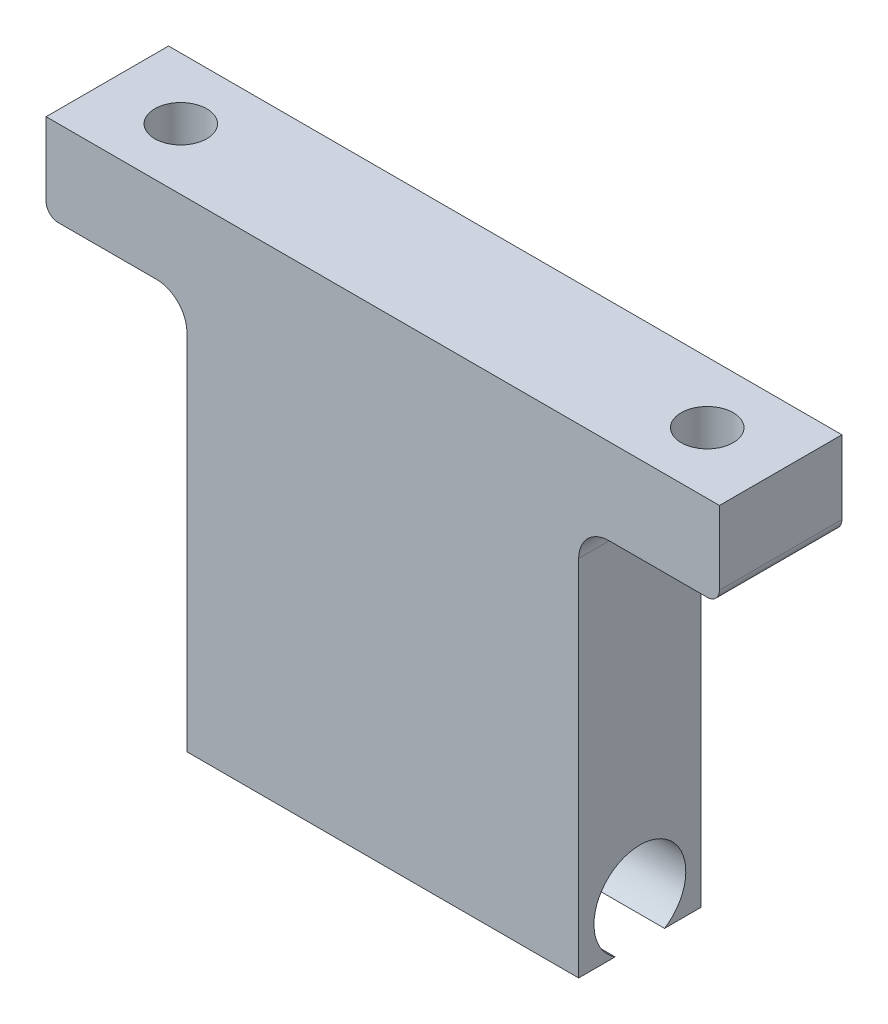
SolidWorks part; units mm, degrees
ref_plane "Front Plane" through (0, 0, 0) normal (0, 0, 1) x (1, 0, 0)
ref_plane "Top Plane" through (0, 0, 0) normal (0, 1, 0) x (1, 0, 0)
ref_plane "Right Plane" through (0, 0, 0) normal (1, 0, 0) x (0, 0, -1)
sketch "Esboço2" plane through (0, 0, 0) normal (0, 0, 1) x (1, 0, 0)
  line L1 (-252, 105.2122) -> (-188, 105.2122)
  line L2 (-252, 105.2122) -> (-252, 164.5682)
  line L4 (-188, 105.2122) -> (-188, 164.5682)
  line L9 (-183, 169.5682) -> (-167, 169.5682)
  line L10 (-165, 171.5682) -> (-165, 183.5682)
  line L11 (-165, 183.5682) -> (-275, 183.5682)
  line L12 (-275, 183.5682) -> (-275, 171.5682)
  line L13 (-273, 169.5682) -> (-257, 169.5682)
  arc A4 (-183, 169.5682) -> (-188, 164.5682) centre (-183, 164.5682) ccw
  arc A5 (-167, 169.5682) -> (-165, 171.5682) centre (-167, 171.5682) ccw
  arc A6 (-275, 171.5682) -> (-273, 169.5682) centre (-273, 171.5682) ccw
  arc A7 (-252, 164.5682) -> (-257, 169.5682) centre (-257, 164.5682) ccw
extrude "Ressalto-extrusão1" add sketch "Esboço2" along normal blind 20
sketch "Esboço4" plane through (-188, 0, 0) normal (1, 0, 0) x (0, 0, -1)
  line L0 (-10, 105.2122) -> (-10, 130.5148) construction
  line L1 (-20, 105.2122) -> (0, 105.2122) construction
  circle A3 centre (-10, 111.5382) radius 7.5
  circle A4 centre (-10, 111.5382) radius 7.5
  dimension "D2" = 0
extrude "Corte-extrusão2" cut sketch "Esboço4" against normal through all
sketch "Esboço5" plane through (0, 183.5682, 0) normal (0, 1, 0) x (1, 0, 0)
  line L0 (-275, -10) -> (-165, -10) construction
  line L1 (-275, -20) -> (-275, 0) construction
  line L2 (-165, -20) -> (-165, 0) construction
  circle A0 centre (-263, -10) radius 4.25
  circle A1 centre (-177, -10) radius 4.25
  point P8 (0, 0)
  point P11 (0, 0)
  point P12 (0, 0)
  dimension "D1" = 8.5
  dimension "D2" = 12
  dimension "D3" = 12
extrude "Corte-extrusão3" cut sketch "Esboço5" against normal through all
sketch "Esboço6" plane through (0, 183.5682, 0) normal (0, 1, 0) x (1, 0, 0)
  line L0 (-220, -20) -> (-220, 0) construction
  line L1 (-165, -20) -> (-275, -20) construction
  line L2 (-165, 0) -> (-275, 0) construction
  line L3 (-205, -10) -> (-235, -10) construction
  line L4 (-205, -17.5) -> (-235, -17.5)
  line L5 (-205, -17.5) -> (-205, -2.5)
  line L6 (-205, -2.5) -> (-235, -2.5)
  line L7 (-235, -17.5) -> (-235, -2.5)
  point P12 (-220, -10)
  point P13 (-220, -10)
  dimension "D1" = 15
  dimension "D2" = 30
